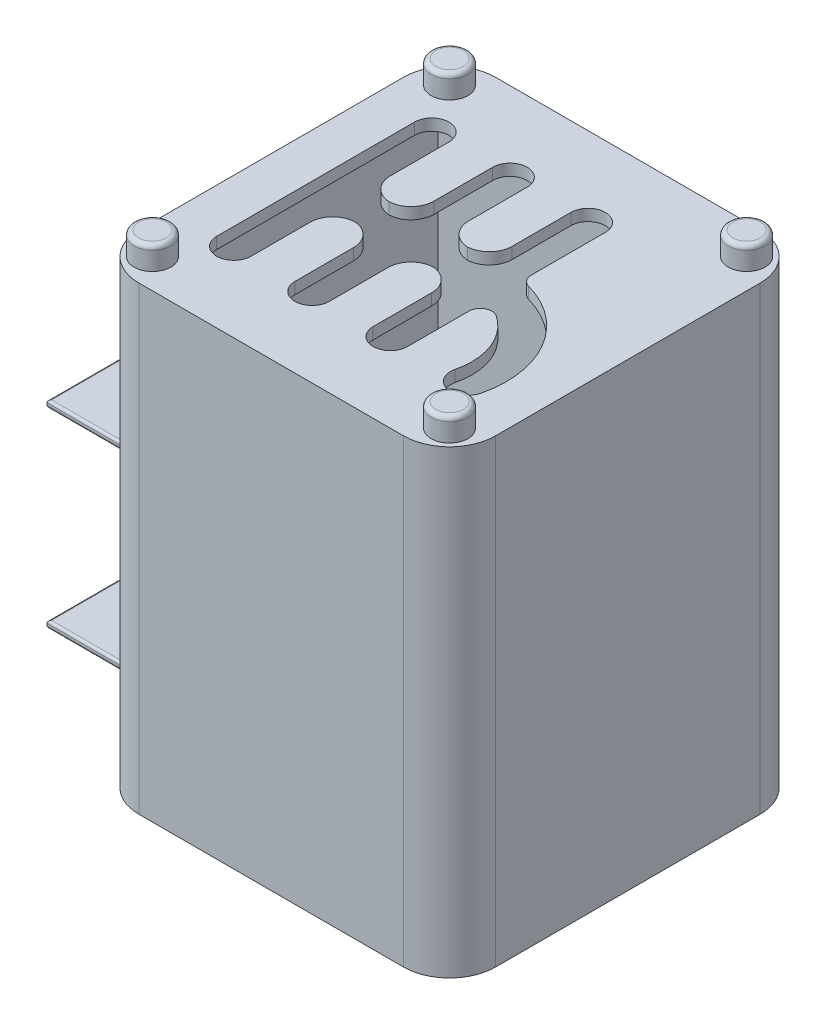
SolidWorks part; units mm, degrees
ref_plane "Płaszczyzna przednia" through (0, 0, 0) normal (0, 0, 1) x (1, 0, 0)
ref_plane "Płaszczyzna górna" through (0, 0, 0) normal (0, 1, 0) x (1, 0, 0)
ref_plane "Płaszczyzna prawa" through (0, 0, 0) normal (1, 0, 0) x (0, 0, -1)
sketch "Szkic1" plane through (0, 0, 0) normal (0, 1, 0) x (1, 0, 0)
  line L1 (-77.5, -77.5) -> (77.5, -77.5)
  line L2 (-77.5, -77.5) -> (-77.5, 77.5)
  line L3 (-77.5, 77.5) -> (77.5, 77.5)
  line L4 (77.5, -77.5) -> (77.5, 77.5)
  line L5 (-77.5, -77.5) -> (77.5, 77.5) construction
  line L6 (-77.5, 77.5) -> (77.5, -77.5) construction
  point P0 (0, 0)
  dimension "D1" = 155
  dimension "D2" = 155
extrude "Dodanie-wyciągnięcie1" add sketch "Szkic1" along normal blind 200
sketch "Szkic2" plane through (0, 200, 0) normal (0, 1, 0) x (1, 0, 0)
  line L0 (-50.7402, -43) -> (-50.7402, 43) construction
  line L1 (-58.2402, -43) -> (-58.2402, 43)
  line L2 (-43.2402, -43) -> (-43.2402, 43)
  line L3 (-16.7402, -43) -> (-16.7402, 43) construction
  line L4 (-24.2402, -43) -> (-24.2402, 43)
  line L5 (-9.2402, -43) -> (-9.2402, 43)
  line L6 (17.2598, -43) -> (17.2598, 43) construction
  line L7 (9.7598, -43) -> (9.7598, 43)
  line L8 (24.7598, -43) -> (24.7598, 43)
  line L9 (0, 0) -> (0, 91.9283) construction
  line L10 (-58.2402, 0) -> (58.2402, 0) construction
  line L12 (-43.2402, -7.5) -> (17.2598, -7.5)
  line L13 (-43.2402, -7.5) -> (-43.2402, 7.5)
  line L14 (-43.2402, 7.5) -> (17.2598, 7.5)
  line L15 (17.2598, -7.5) -> (17.2598, 7.5)
  arc A0 (-58.2402, -43) -> (-43.2402, -43) centre (-50.7402, -43) ccw
  arc A1 (-43.2402, 43) -> (-58.2402, 43) centre (-50.7402, 43) ccw
  arc A2 (-24.2402, -43) -> (-9.2402, -43) centre (-16.7402, -43) ccw
  arc A3 (-9.2402, 43) -> (-24.2402, 43) centre (-16.7402, 43) ccw
  arc A4 (9.7598, -43) -> (24.7598, -43) centre (17.2598, -43) ccw
  arc A5 (24.7598, 43) -> (9.7598, 43) centre (17.2598, 43) ccw
  arc A8 (50.9576, -43) -> (17.2598, 0) centre (17.2598, -34.704) ccw construction
  arc A9 (58.2402, -44.7929) -> (17.2598, 7.5) centre (17.2598, -34.704) ccw
  arc A10 (43.6751, -41.2071) -> (17.2598, -7.5) centre (17.2598, -34.704) ccw
  arc A11 (43.6751, -41.2071) -> (58.2402, -44.7929) centre (50.9576, -43) ccw
  arc A12 (17.2598, 7.5) -> (17.2598, -7.5) centre (17.2598, 0) ccw
  point P2 (-50.7402, 0)
  point P8 (-16.7402, 0)
  point P15 (17.2598, 0)
  point P24 (44.5753, -13.2977)
  dimension "D4" = 15
  dimension "D1" = 15
  dimension "D2" = 15
  dimension "D3" = 15
  dimension "D5" = 19
  dimension "D6" = 19
  dimension "D7" = 86
  dimension "D8" = 19
extrude "Wytnij-wyciągnięcie1" cut sketch "Szkic2" against normal blind 90 contours L14 L2 L12 L4 | L4 A2 L5 L12 | L14 L4 L12 L5 | L5 A3 L4 L14 | L14 L5 L12 L7 | A10 L8 A9 L15 | L15 A12 | A12 L14 L7 | A12 L7 L12 | A9 L8 A5 L7 L14 | L8 A10 L12 L7 A4 | A10 A11 A9 L8 | L2 A1 L1 A0 region at (-33.7402, 200, 0) region at (-16.7402, 200, 28.2291) region at (-16.7402, 200, 0) region at (-16.7402, 200, -28.2291) region at (0.2598, 200, 0) region at (17.236, 200, 28.3154) region at (11.4351, 200, 5.8247) region at (11.4351, 200, -5.8247) region at (17.275, 200, -28.1728) region at (14.0767, 200, 0) region at (21.0255, 200, 0.2879) region at (44.7198, 200, 20.6509)
fillet "Zaokrąglenie1" radius 20 4 edges at (-77.5, 100, -77.5) (-77.5, 100, 77.5) (77.5, 100, -77.5) (77.5, 100, 77.5)
sketch "Szkic4" plane through (0, 200, 0) normal (0, 1, 0) x (1, 0, 0)
  line L0 (-71.6421, -71.6421) -> (-57.5, -57.5) construction
  arc A2 (-77.5, -57.5) -> (-57.5, -77.5) centre (-57.5, -57.5) ccw construction
  circle A3 centre (-64.5711, -64.5711) radius 8
  circle A4 centre (-64.5711, 64.5711) radius 8
  circle A5 centre (64.5711, 64.5711) radius 8
  circle A6 centre (64.5711, -64.5711) radius 8
  point P17 (0, 0)
  dimension "D1" = 16
  dimension "D2" = 4
extrude "Dodanie-wyciągnięcie2" add sketch "Szkic4" along normal blind 10
fillet "Zaokrąglenie2" radius 2 4 edges at (64.5711, 210, 72.5711) (64.5711, 210, -56.5711) (-64.5711, 210, -56.5711) (-64.5711, 210, 72.5711)
ref_plane "Płaszczyzna1" through (0, 0, 57.5) normal (0, 0, 1) x (1, 0, 0)
sketch "Szkic5" plane through (0, 0, 57.5) normal (0, 0, 1) x (1, 0, 0)
  line L0 (-77.5, 0) -> (-77.5, 200) construction
  line L1 (-67.5, 25) -> (67.5, 25)
  line L2 (-67.5, 25) -> (-67.5, 195)
  line L3 (-67.5, 195) -> (67.5, 195)
  line L4 (67.5, 25) -> (67.5, 195)
  line L5 (77.5, 200) -> (77.5, 0) construction
  line L6 (-57.5, 200) -> (57.5, 200) construction
  line L7 (-57.5, 0) -> (57.5, 0) construction
  dimension "D1" = 10
  dimension "D2" = 10
  dimension "D3" = 5
  dimension "D4" = 25
extrude "Wytnij-wyciągnięcie2" cut sketch "Szkic5" against normal blind 120
sketch "Szkic6" plane through (0, 25, 0) normal (0, 1, 0) x (1, 0, 0)
  circle A0 centre (-16.7402, 0) radius 10
  arc A2 (-9.2402, 43) -> (-24.2402, 43) centre (-16.7402, 43) ccw construction
  point P9 (-16.7402, 50.5)
  dimension "D2" = 20
extrude "Dodanie-wyciągnięcie3" add sketch "Szkic6" along normal blind 80
sketch "Szkic7" plane through (0, 105, 0) normal (0, 1, 0) x (1, 0, 0)
  line L0 (-16.7402, 8) -> (-16.7402, -8)
  arc A0 (-16.7402, 8) -> (-16.7402, -8) centre (-16.7402, 0) cw
  dimension "D1" = 8
revolve "Wycięcie-obrót1" cut sketch "Szkic7" angle 360 about L0
sketch "Szkic8" plane through (-77.5, 0, 0) normal (-1, 0, 0) x (0, 0, 1)
  line L0 (-57.5, 200) -> (-57.5, 0) construction
  line L1 (-57.5, 116) -> (57.5, 116)
  line L2 (-57.5, 116) -> (-57.5, 113)
  line L3 (-57.5, 113) -> (57.5, 113)
  line L4 (57.5, 116) -> (57.5, 113)
  line L5 (57.5, 0) -> (57.5, 200) construction
  line L6 (-57.5, 0) -> (57.5, 0) construction
  line L7 (57.5, 30) -> (-57.5, 30)
  line L8 (57.5, 30) -> (57.5, 33)
  line L9 (57.5, 33) -> (-57.5, 33)
  line L10 (-57.5, 30) -> (-57.5, 33)
  dimension "D1" = 3
  dimension "D2" = 3
  dimension "D3" = 80
  dimension "D4" = 30
extrude "Dodanie-wyciągnięcie4" add sketch "Szkic8" along normal blind 40
sketch "Szkic9" plane through (0, 116, 0) normal (0, 1, 0) x (1, 0, 0)
  line L1 (-145.6746, 0) -> (93.5883, 0) construction
  line L2 (-117.5, 57.5) -> (-77.5, 57.5) construction
  circle A0 centre (-97.5, 37.5) radius 4
  circle A2 centre (-97.5, -37.5) radius 4
  point P7 (-97.5, 57.5)
  dimension "D1" = 8
  dimension "D2" = 75
extrude "Wytnij-wyciągnięcie3" cut sketch "Szkic9" against normal blind 100
fillet "Zaokrąglenie3" radius 1 12 edges at (-97.5, 30, 57.5) (-97.5, 33, 57.5) (-117.5, 33, 0) (-117.5, 30, 0) (-97.5, 33, -57.5) (-97.5, 30, -57.5) (-97.5, 113, -57.5) (-97.5, 116, -57.5) (-117.5, 113, 0) (-117.5, 116, 0) (-97.5, 116, 57.5) (-97.5, 113, 57.5)
sketch "Szkic10" plane through (0, 0, 0) normal (0, -1, 0) x (1, 0, 0)
  line L1 (-55, -55) -> (55, -55) construction
  line L2 (-55, -55) -> (-55, 55) construction
  line L3 (-55, 55) -> (55, 55) construction
  line L4 (55, -55) -> (55, 55) construction
  line L5 (-55, -55) -> (55, 55) construction
  line L6 (-55, 55) -> (55, -55) construction
  point P0 (0, 0)
  dimension "D1" = 110
  dimension "D2" = 110
hole_wizard "Otwory ustalające Ø8.0mm1" positions "Szkic11" profile "Szkic12" hole size "Ø8.0" standard "ISO" end condition up to next
sketch "Szkic11" plane through (0, 0, 0) normal (0, -1, 0) x (-1, 0, 0)
  point P0 (55, 55)
  point P3 (55, -55)
  point P6 (-55, -55)
  point P9 (-55, 55)
sketch "Szkic12" plane through (-55, 0, -55) normal (1, 0, 0) x (0, 0, -1)
  line L0 (0, 0) -> (0, 25)
  line L1 (0, 25) -> (4, 25)
  line L2 (4, 25) -> (4, 0)
  line L5 (4, 0) -> (0, 0)
  line L11 (0, -6.35) -> (0, 107.95) construction
  dimension "Średnica otworu na wylot" = 8
  dimension "Głębokość otworu na wylot" = 25
fillet "Zaokrąglenie4" radius 10 8 edges at (-9.2402, 197.5, 7.5) (9.7598, 197.5, 7.5) (9.7598, 197.5, -7.5) (-9.2402, 197.5, -7.5) (-24.2402, 197.5, -7.5) (-43.2402, 197.5, -7.5) (-24.2402, 197.5, 7.5) (-43.2402, 197.5, 7.5)
fillet "Zaokrąglenie5" radius 5 2 edges at (24.7598, 197.5, -6.8282) (24.7598, 197.5, 8.5543)
